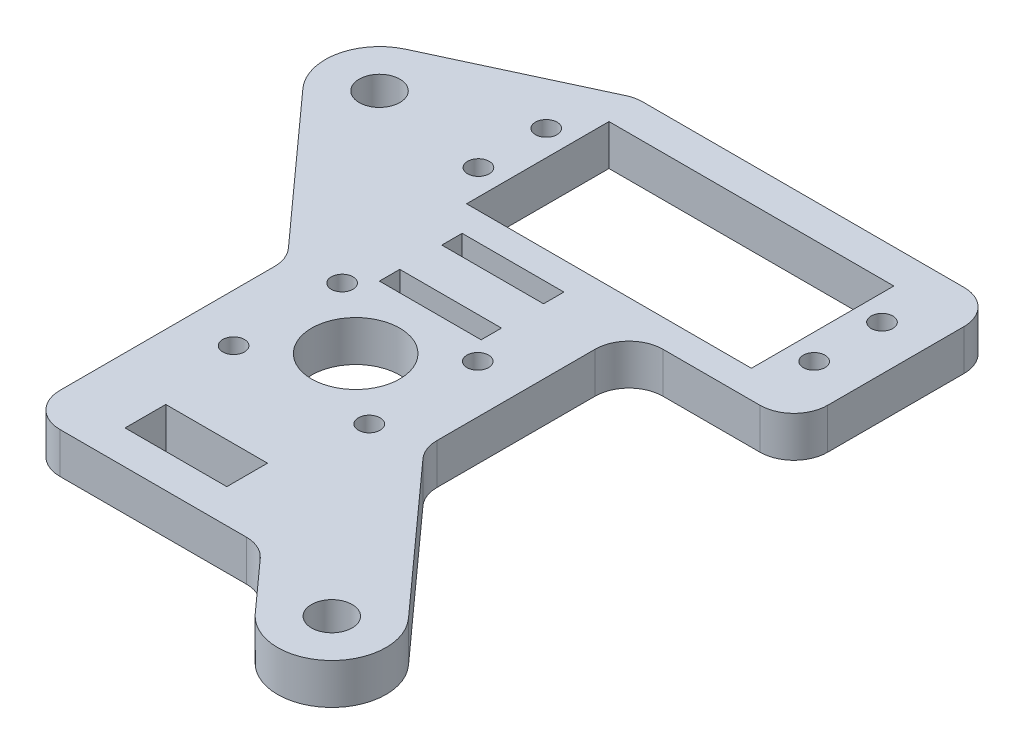
SolidWorks part; units mm, degrees
material "MDF"
ref_plane "Plano frontal" through (0, 0, 0) normal (0, 0, 1) x (1, 0, 0)
ref_plane "Plano superior" through (0, 0, 0) normal (0, 1, 0) x (1, 0, 0)
ref_plane "Plano direito" through (0, 0, 0) normal (1, 0, 0) x (0, 0, -1)
ref_plane "Plano1" through (0, -6, 0) normal (0, -1, 0) x (1, 0, 0)
sketch "Esboço1" plane through (0, -6, 0) normal (0, -1, 0) x (1, 0, 0)
  line L0 (30.7936, -136.5537) -> (52.8946, -146.8291)
  line L1 (55.0026, -147.2952) -> (102.3526, -147.2952)
  line L2 (107.3526, -142.2952) -> (107.3526, -122.2)
  line L3 (102.3526, -117.2) -> (88.05, -117.2)
  line L4 (83.05, -112.2) -> (83.05, -88.8837)
  line L5 (84.3343, -85.538) -> (103.6789, -64.0537)
  line L6 (91.7885, -53.3476) -> (85.0372, -60.8457)
  line L7 (81.3215, -62.5) -> (53.85, -62.5)
  line L8 (48.85, -67.5) -> (48.85, -99.1163)
  line L9 (47.5657, -102.462) -> (28.2211, -123.9463)
  line L10 (73.45, -114.2) -> (73.45, -117.2)
  line L11 (73.45, -117.2) -> (58.45, -117.2)
  line L12 (58.45, -117.2) -> (58.45, -114.2)
  line L13 (58.45, -114.2) -> (73.45, -114.2)
  line L14 (58.45, -108) -> (58.45, -105)
  line L15 (58.45, -105) -> (73.45, -105)
  line L16 (73.45, -105) -> (73.45, -108)
  line L17 (73.45, -108) -> (58.45, -108)
  line L18 (58.45, -67.5) -> (73.45, -67.5)
  line L19 (73.45, -67.5) -> (73.45, -73.5)
  line L20 (73.45, -73.5) -> (58.45, -73.5)
  line L21 (58.45, -73.5) -> (58.45, -67.5)
  line L22 (55.0026, -142.2952) -> (55.0026, -121.2952)
  line L23 (55.0026, -121.2952) -> (97.0026, -121.2952)
  line L24 (97.0026, -121.2952) -> (97.0026, -142.2952)
  line L25 (97.0026, -142.2952) -> (55.0026, -142.2952)
  arc A0 (52.8946, -146.8291) -> (55.0026, -147.2952) centre (55.0026, -142.2952) ccw
  arc A1 (102.3526, -147.2952) -> (107.3526, -142.2952) centre (102.3526, -142.2952) ccw
  arc A2 (107.3526, -122.2) -> (102.3526, -117.2) centre (102.3526, -122.2) ccw
  arc A3 (88.05, -117.2) -> (83.05, -112.2) centre (88.05, -112.2) cw
  arc A4 (83.05, -88.8837) -> (84.3343, -85.538) centre (88.05, -88.8837) cw
  arc A5 (103.6789, -64.0537) -> (91.7885, -53.3476) centre (97.7337, -58.7006) ccw
  arc A6 (85.0372, -60.8457) -> (81.3215, -62.5) centre (81.3215, -57.5) cw
  arc A7 (53.85, -62.5) -> (48.85, -67.5) centre (53.85, -67.5) ccw
  arc A8 (48.85, -99.1163) -> (47.5657, -102.462) centre (43.85, -99.1163) cw
  arc A9 (28.2211, -123.9463) -> (30.7936, -136.5537) centre (34.1663, -129.2994) ccw
  circle A10 centre (65.95, -94) radius 6.5
  circle A11 centre (55.95, -102) radius 1.6
  circle A12 centre (55.95, -86) radius 1.6
  circle A13 centre (75.95, -102) radius 1.6
  circle A14 centre (75.95, -86) radius 1.6
  circle A15 centre (100.7526, -126.7952) radius 1.6
  circle A16 centre (100.7526, -136.7952) radius 1.6
  circle A17 centre (51.2526, -126.7952) radius 1.6
  circle A18 centre (51.2526, -136.7952) radius 1.6
  circle A19 centre (34.1663, -129.2994) radius 3
  circle A20 centre (97.7337, -58.7006) radius 3
extrude "Ressalto-extrusão1" add sketch "Esboço1" against normal blind 6
